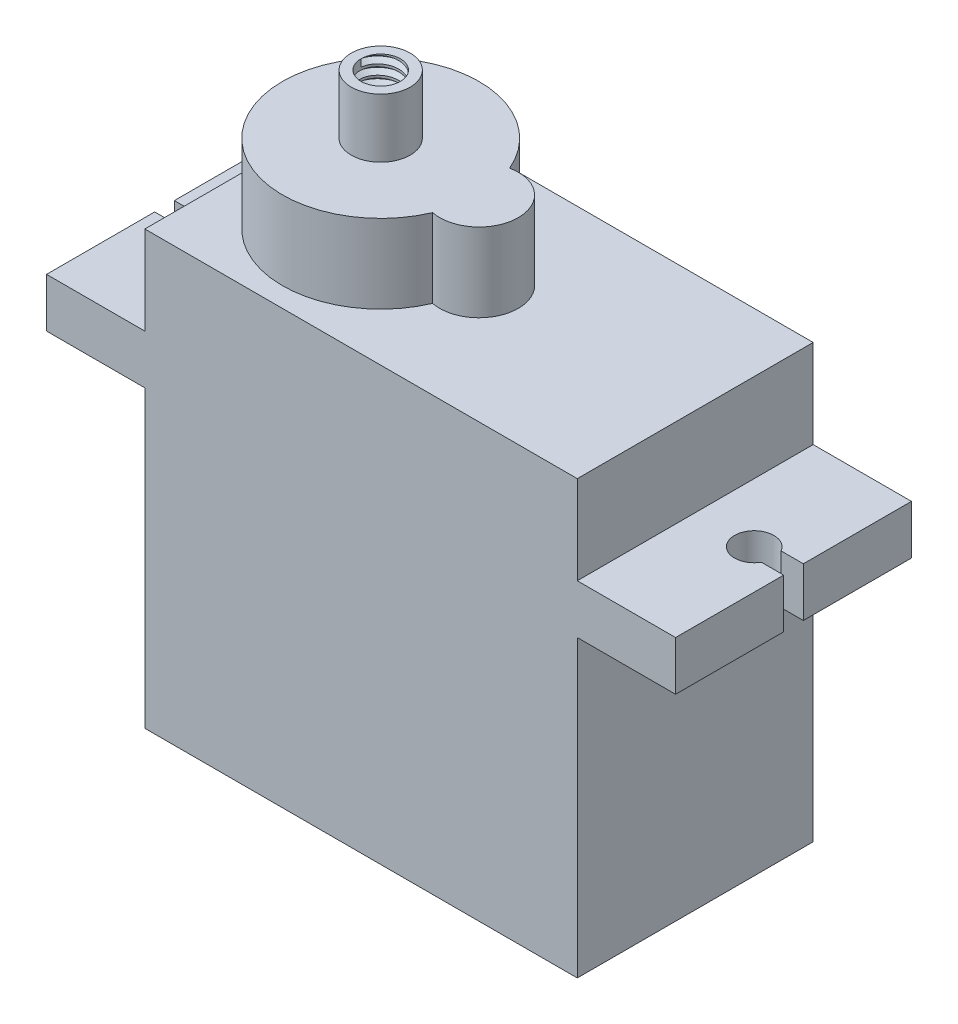
SolidWorks part; units mm, degrees
ref_plane "Front Plane" through (0, 0, 0) normal (0, 0, 1) x (1, 0, 0)
ref_plane "Top Plane" through (0, 0, 0) normal (0, 1, 0) x (1, 0, 0)
ref_plane "Right Plane" through (0, 0, 0) normal (1, 0, 0) x (0, 0, -1)
sketch "Sketch1" plane through (0, 0, 0) normal (0, 1, 0) x (1, 0, 0)
  line L1 (-11, 6) -> (11, 6)
  line L2 (-11, 6) -> (-11, -6)
  line L3 (-11, -6) -> (11, -6)
  line L4 (11, 6) -> (11, -6)
  line L5 (-11, 6) -> (11, -6) construction
  line L6 (-11, -6) -> (11, 6) construction
  point P0 (0, 0)
  dimension "D1" = 22
  dimension "D2" = 12
extrude "Body" add sketch "Sketch1" along normal blind 22 contours L2 L3 L4 L1
ref_plane "Plane1" through (0, 22, 0) normal (0, 1, 0) x (1, 0, 0)
sketch "Sketch2" plane through (0, 22, 0) normal (0, 1, 0) x (1, 0, 0)
  arc A0 (-0.4, 1.9596) -> (-0.4, -1.9596) centre (-5, 0) ccw
  arc A1 (-0.4, -1.9596) -> (-0.4, 1.9596) centre (0, 0) ccw
  dimension "D1" = 10
  dimension "D3" = 4
  dimension "D2" = 5
extrude "Hub" add sketch "Sketch2" along normal blind 4 contours A0 A1
ref_plane "Plane2" through (0, 26, 0) normal (0, 1, 0) x (1, 0, 0)
sketch "Sketch3" plane through (0, 26, 0) normal (0, 1, 0) x (1, 0, 0)
  circle A0 centre (-5, 0) radius 1.5
  dimension "D1" = 3
extrude "Axle" add sketch "Sketch3" along normal blind 3
ref_plane "Plane3" through (0, 15, 0) normal (0, 1, 0) x (1, 0, 0)
sketch "Sketch4" plane through (0, 15, 0) normal (0, 1, 0) x (1, 0, 0)
  line L1 (-16, 6) -> (16, 6)
  line L2 (-16, 6) -> (-16, -6)
  line L3 (-16, -6) -> (16, -6)
  line L4 (16, 6) -> (16, -6)
  line L5 (-16, 6) -> (16, -6) construction
  line L6 (-16, -6) -> (16, 6) construction
  point P0 (0, 0)
  dimension "D1" = 12
  dimension "D2" = 32
extrude "Fin" add sketch "Sketch4" along normal blind 2.5
ref_plane "Plane4" through (-11, 0, 0) normal (-1, 0, 0) x (0, 0, 1)
sketch "Sketch5" plane through (-11, 0, 0) normal (-1, 0, 0) x (0, 0, 1)
  line L1 (-2, 4.5) -> (2, 4.5)
  line L2 (-2, 4.5) -> (-2, 3.5)
  line L3 (-2, 3.5) -> (2, 3.5)
  line L4 (2, 4.5) -> (2, 3.5)
  line L5 (-2, 4.5) -> (2, 3.5) construction
  line L6 (-2, 3.5) -> (2, 4.5) construction
  point P0 (0, 4)
  dimension "D1" = 4
  dimension "D2" = 1
  dimension "D3" = 4
extrude "Wire out" add sketch "Sketch5" along normal blind 0.5
sketch "Sketch6" plane through (0, 15, 0) normal (0, 1, 0) x (1, 0, 0)
  line L0 (-16, 6) -> (-16, -6) construction
  line L1 (0, -6.6) -> (0, 6.6) construction
  circle A0 centre (-14, 0) radius 1
  circle A1 centre (14, 0) radius 1
  point P4 (-16, 0)
  dimension "D1" = 2
  dimension "D2" = 2
extrude "Hole for screws" cut sketch "Sketch6" along normal up to next
ref_plane "Plane5" through (0, 29, 0) normal (0, 1, 0) x (1, 0, 0)
sketch "Sketch7" plane through (0, 29, 0) normal (0, 1, 0) x (1, 0, 0)
  circle A0 centre (-5, 0) radius 1
  dimension "D1" = 2
extrude "Cut-Extrude1" cut sketch "Sketch7" against normal blind 6 contours A0
sketch "Sketch8" plane through (0, 15, 0) normal (0, 1, 0) x (1, 0, 0)
  line L0 (-16.5, 0.5) -> (-14.5, 0.5)
  line L1 (-14.5, 0.5) -> (-14.5, -0.5)
  line L2 (-14.5, -0.5) -> (-16.5, -0.5)
  line L3 (-16.5, -0.5) -> (-16.5, 0.5)
  line L4 (-11, 6) -> (-16, 6) construction
  line L5 (-11, 6) -> (-11, -6) construction
  line L6 (0, -6.6) -> (0, 6.6) construction
  line L7 (14.5, 0.5) -> (14.5, -0.5)
  line L8 (16.5, 0.5) -> (14.5, 0.5)
  line L9 (16.5, -0.5) -> (16.5, 0.5)
  line L10 (14.5, -0.5) -> (16.5, -0.5)
  dimension "D1" = 1
  dimension "D2" = 2
  dimension "D3" = 5.5
  dimension "D4" = 3.5
extrude "Cut-Extrude2" cut sketch "Sketch8" along normal up to next
thread "Thread1" pitch 0.5 method cut profile "Thread Profile1" start angle 0, offset 0, length 0, pitch 0.5, diameter 2
ref_plane "Plane6" through (-6, 29, 0) normal (0, 0, 1) x (-1, 0, 0)
sketch "Thread Profile1" plane through (-6, 29, 0) normal (0, 0, 1) x (-1, 0, 0)
  line L0 (0, 0) -> (0, 0.5) construction
  line L1 (0, 0) -> (0.2706, 0.1562)
  line L2 (0.2706, 0.1562) -> (0.2706, 0.2187)
  line L3 (0.2706, 0.2187) -> (0, 0.375)
  line L4 (0.2706, 0.1875) -> (0, 0.1875) construction
  line L11 (0, 0) -> (0, 0.375)
  point P2 (0, 0)
  dimension "Pitch" = 0.5
  dimension "Profile_Angle" = 60
  dimension "Profile_Land" = 0.0625
  dimension "Profile_Height" = 0.2706
